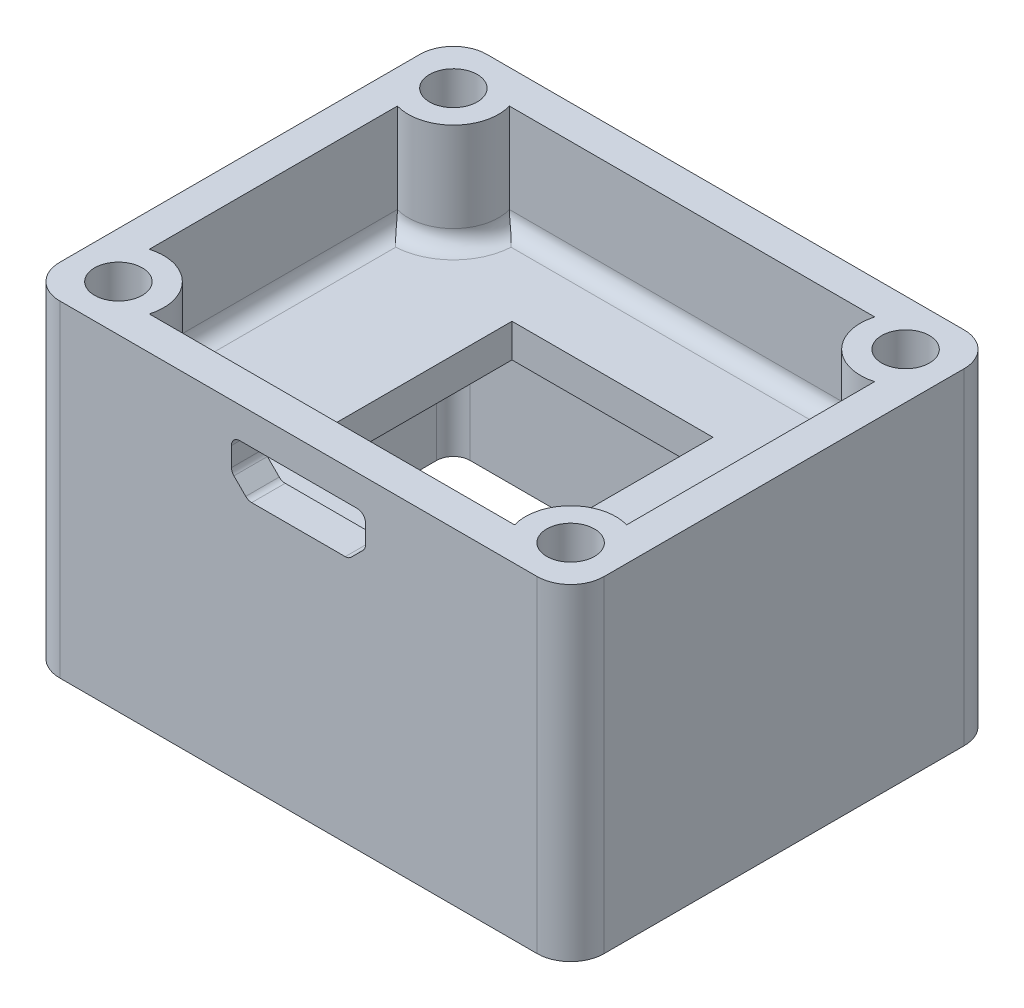
SolidWorks part; units mm, degrees
material "ABS"
ref_plane "Front" through (0, 0, 0) normal (0, 0, 1) x (1, 0, 0)
ref_plane "Top" through (0, 0, 0) normal (0, 1, 0) x (1, 0, 0)
ref_plane "Right" through (0, 0, 0) normal (1, 0, 0) x (0, 0, -1)
sketch "草图1" plane through (0, 0, 0) normal (0, 1, 0) x (1, 0, 0)
  line L0 (-14.25, 10.75) -> (-16.25, 10.75) construction
  line L5 (-14.25, 10.75) -> (14.25, 10.75)
  line L6 (-14.25, 10.75) -> (-14.25, -10.75)
  line L11 (-14.25, -10.75) -> (14.25, -10.75)
  line L12 (14.25, 10.75) -> (14.25, -10.75)
  line L13 (-14.25, 10.75) -> (14.25, -10.75) construction
  line L14 (-14.25, -10.75) -> (14.25, 10.75) construction
  line L15 (-16.25, 12.75) -> (16.25, 12.75)
  line L16 (-16.25, 12.75) -> (-16.25, -12.75)
  line L17 (-16.25, -12.75) -> (16.25, -12.75)
  line L18 (16.25, 12.75) -> (16.25, -12.75)
  line L19 (-16.25, 12.75) -> (16.25, -12.75) construction
  line L20 (-16.25, -12.75) -> (16.25, 12.75) construction
  line L21 (-14.25, 10.75) -> (-14.25, 12.75) construction
  point P0 (0, 0)
  point P6 (0, 0)
  dimension "D3" = 28.5
  dimension "D2" = 2
  dimension "D4" = 21.5
extrude "凸台-拉伸1" add sketch "草图1" along normal blind 13.2
sketch "草图2" plane through (0, 13.2, 0) normal (0, 1, 0) x (1, 0, 0)
  line L1 (-14.25, 10.75) -> (14.25, 10.75)
  line L2 (-14.25, 10.75) -> (-14.25, -10.75)
  line L3 (-14.25, -10.75) -> (14.25, -10.75)
  line L4 (14.25, 10.75) -> (14.25, -10.75)
  line L5 (-14.25, 10.75) -> (14.25, -10.75) construction
  line L6 (-14.25, -10.75) -> (14.25, 10.75) construction
  line L7 (-6, 6) -> (6, 6)
  line L8 (-6, 6) -> (-6, -6)
  line L9 (-6, -6) -> (6, -6)
  line L10 (6, 6) -> (6, -6)
  line L11 (-6, 6) -> (6, -6) construction
  line L12 (-6, -6) -> (6, 6) construction
  point P0 (0, 0)
  point P7 (0, 0)
  point P8 (0, 0)
  dimension "D1" = 12
extrude "凸台-拉伸2" add sketch "草图2" against normal blind 2
sketch "草图3" plane through (0, 13.2, 0) normal (0, 1, 0) x (1, 0, 0)
  line L0 (0, 0) -> (-16.25, 0) construction
  line L1 (-16.25, 12.75) -> (-16.25, -12.75) construction
  line L2 (-16.25, -12.75) -> (-16.25, 12.75)
  line L3 (-16.25, 12.75) -> (16.25, 12.75)
  line L4 (16.25, 12.75) -> (16.25, -0.0404)
  line L5 (16.25, -12.75) -> (16.25, 12.75) construction
  line L7 (14.25, 0.0137) -> (14.25, 10.75)
  line L8 (14.25, 10.75) -> (-14.25, 10.75)
  line L9 (-14.25, 10.75) -> (-14.25, -10.75)
  line L10 (14.25, -10.75) -> (-14.25, -10.75)
  line L11 (14.25, 0.0137) -> (14.25, -10.75)
  line L13 (16.25, -12.75) -> (16.25, -0.0404)
  line L14 (-16.25, -12.75) -> (16.25, -12.75)
  line L15 (14.25, 10.75) -> (-14.25, 10.75) construction
  line L16 (-14.25, 10.75) -> (-14.25, -10.75) construction
  line L17 (14.25, -10.75) -> (14.25, 10.75) construction
  point P17 (-14.25, 0)
extrude "凸台-拉伸3" add sketch "草图3" along normal blind 6.3
sketch "草图6" plane through (0, 19.5, 0) normal (0, 1, 0) x (1, 0, 0)
  line L0 (16.25, 0) -> (0, 0) construction
  line L2 (0, 0) -> (0, 12.75) construction
  line L4 (16.25, -12.75) -> (16.25, 12.75) construction
  line L5 (16.25, 12.75) -> (-16.25, 12.75) construction
  circle A0 centre (13.5, 10) radius 2.7
  circle A1 centre (13.5, -10) radius 2.7
  circle A2 centre (-13.5, -10) radius 2.7
  circle A3 centre (-13.5, 10) radius 2.7
  dimension "D1" = 5.4
  dimension "D2" = 27
  dimension "D3" = 20
extrude "凸台-拉伸4" add sketch "草图6" against normal up to next
sketch "草图7" plane through (0, 19.5, 0) normal (0, 1, 0) x (1, 0, 0)
  line L0 (0, 12.75) -> (0, 0) construction
  line L2 (0, 0) -> (16.25, 0) construction
  line L4 (16.25, 12.75) -> (-16.25, 12.75) construction
  line L5 (16.25, -12.75) -> (16.25, 12.75) construction
  circle A0 centre (13.5, 10) radius 1.425
  circle A1 centre (13.5, -10) radius 1.425
  circle A2 centre (-13.5, -10) radius 1.425
  circle A3 centre (-13.5, 10) radius 1.425
  dimension "D1" = 2.85
extrude "切除-拉伸3" cut sketch "草图7" against normal blind 5.5
sketch "草图10" plane through (0, 11.2, 0) normal (0, -1, 0) x (1, 0, 0)
  line L1 (-7.1, 7.1) -> (7.1, 7.1)
  line L2 (-7.1, 7.1) -> (-7.1, -7.1)
  line L3 (-7.1, -7.1) -> (7.1, -7.1)
  line L4 (7.1, 7.1) -> (7.1, -7.1)
  line L5 (-7.1, 7.1) -> (7.1, -7.1) construction
  line L6 (-7.1, -7.1) -> (7.1, 7.1) construction
  line L7 (-7.9, 7.9) -> (7.9, 7.9)
  line L8 (-7.9, 7.9) -> (-7.9, -7.9)
  line L9 (-7.9, -7.9) -> (7.9, -7.9)
  line L10 (7.9, 7.9) -> (7.9, -7.9)
  line L11 (-7.9, 7.9) -> (7.9, -7.9) construction
  line L12 (-7.9, -7.9) -> (7.9, 7.9) construction
  point P11 (0, 0)
  point P13 (0, 0)
  dimension "D1" = 14.2
  dimension "D2" = 0.8
extrude "凸台-拉伸5" add sketch "草图10" along normal blind 0.8 contours L10 L7 L8 L9 L1 L4 L3 L2 region at (0, 11.2, 7.6766)
sketch "草图11" plane through (0, 0, 12.75) normal (0, 0, 1) x (1, 0, 0)
  line L0 (0, 0) -> (0, 19.5) construction
  line L1 (-4, 17.65) -> (4, 17.65)
  line L2 (4, 17.65) -> (4, 15.8)
  line L3 (4, 15.8) -> (3, 14.8)
  line L4 (3, 14.8) -> (-3, 14.8)
  line L5 (-4, 15.8) -> (-3, 14.8)
  line L6 (-4, 17.65) -> (-4, 15.8)
  line L7 (-16.25, 19.5) -> (16.25, 19.5) construction
  line L8 (-10.9063, 13.2) -> (10.9063, 13.2) construction
  point P7 (0, 14.8)
  point P9 (0, 17.65)
  dimension "D1" = 8
  dimension "D2" = 135
  dimension "D3" = 1
  dimension "D4" = 1.6
  dimension "D5" = 2.85
extrude "切除-拉伸5" cut sketch "草图11" against normal blind 3
fillet "圆角6" radius 0.5 6 edges at (4, 15.8, 11.75) (3, 14.8, 11.75) (-3, 14.8, 11.75) (-4, 15.8, 11.75) (-4, 17.65, 11.75) (4, 17.65, 11.75)
fillet "圆角3" radius 0.95 8 edges at (0, 13.2, -10.75) (11.5908, 13.2, -8.0908) (11.5908, 13.2, 8.0908) (0, 13.2, 10.75) (-11.5908, 13.2, 8.0908) (-14.25, 13.2, 0) (-11.5908, 13.2, -8.0908) (14.25, 13.2, 0)
fillet "圆角1" radius 2 4 edges at (16.25, 9.75, -12.75) (-16.25, 9.75, 12.75) (16.25, 9.75, 12.75) (-16.25, 9.75, -12.75)
fillet "圆角2" radius 1 4 edges at (14.25, 5.6, -10.75) (-14.25, 5.6, -10.75) (-14.25, 5.6, 10.75) (14.25, 5.6, 10.75)
